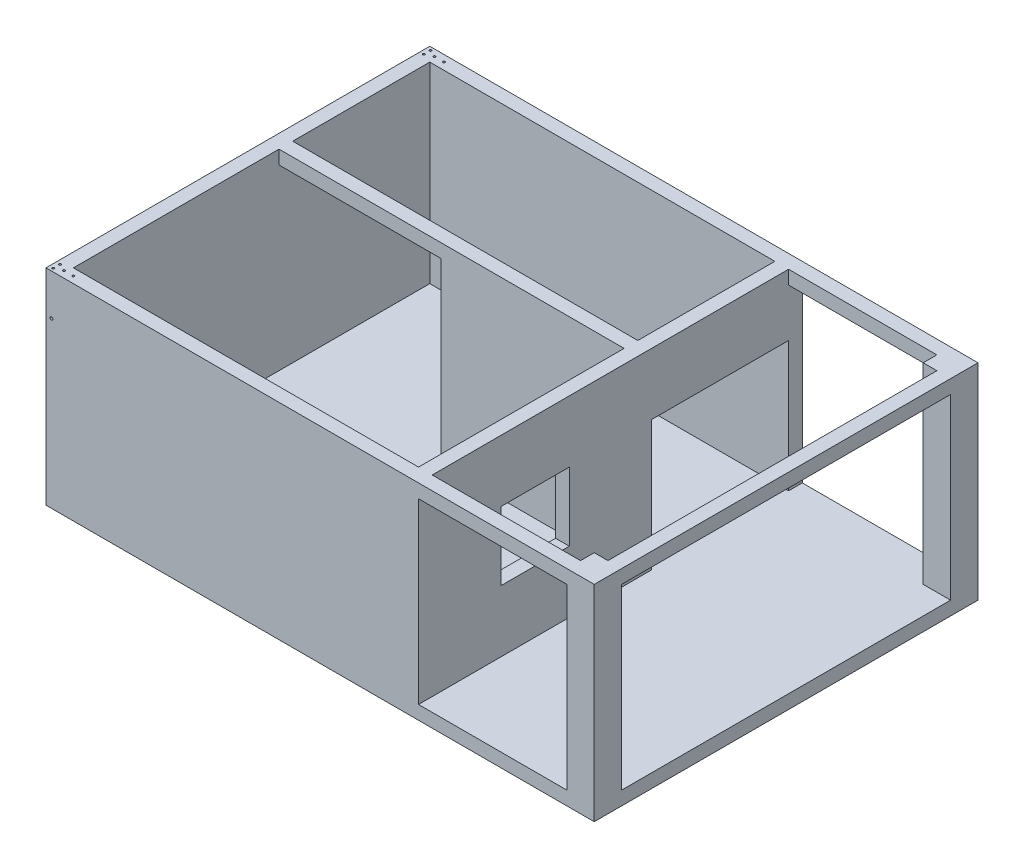
SolidWorks part; units mm, degrees
material "Pine"
ref_plane "Front Plane" through (0, 0, 0) normal (0, 0, 1) x (1, 0, 0)
ref_plane "Top Plane" through (0, 0, 0) normal (0, 1, 0) x (1, 0, 0)
ref_plane "Right Plane" through (0, 0, 0) normal (1, 0, 0) x (0, 0, -1)
sketch "Sketch1" plane through (0, 0, 0) normal (0, 1, 0) x (1, 0, 0)
  line L1 (0, 0) -> (2000, 0)
  line L2 (0, 0) -> (0, 1400)
  line L3 (0, 1400) -> (2000, 1400)
  line L4 (2000, 0) -> (2000, 1400)
  dimension "D1" = 2000
  dimension "D2" = 1400
extrude "Boss-Extrude1" add sketch "Sketch1" along normal blind 50
sketch "Sketch2" plane through (0, 50, 0) normal (0, 1, 0) x (1, 0, 0)
  line L0 (0, 700) -> (2000, 700) construction
  line L1 (2000, 1400) -> (1900, 1400)
  line L2 (2000, 1400) -> (2000, 1300)
  line L3 (2000, 1300) -> (1900, 1300)
  line L4 (1900, 1400) -> (1900, 1300)
  line L5 (0, 1400) -> (0, 0) construction
  line L6 (2000, 0) -> (2000, 1400) construction
  line L7 (2000, 100) -> (1900, 100)
  line L8 (1900, 0) -> (1900, 100)
  line L9 (2000, 0) -> (1900, 0)
  line L10 (2000, 0) -> (2000, 100)
  line L11 (0, 1350) -> (1359, 1350)
  line L12 (0, 0) -> (1359, 0)
  line L13 (0, 0) -> (0, 50)
  line L14 (0, 50) -> (1359, 50)
  line L15 (1359, 0) -> (1359, 50)
  line L16 (1359, 1400) -> (1359, 1350)
  line L17 (0, 1400) -> (1359, 1400)
  line L18 (0, 1400) -> (0, 1350)
  line L20 (0, 1350) -> (50, 1350)
  line L21 (0, 1350) -> (0, 50)
  line L22 (0, 50) -> (50, 50)
  line L23 (50, 1350) -> (50, 50)
  line L24 (641, 850) -> (1359, 850)
  line L25 (641, 850) -> (641, 800)
  line L26 (641, 800) -> (1359, 800)
  line L27 (1359, 850) -> (1359, 800)
  dimension "D1" = 100
  dimension "D2" = 100
  dimension "D3" = 1359
  dimension "D4" = 50
  dimension "D5" = 50
  dimension "D6" = 718
  dimension "D7" = 50
  dimension "D8" = 591
  dimension "D9" = 500
extrude "Boss-Extrude2" add sketch "Sketch2" along normal blind 700 contours L11 L16 L17 L18 | L21 L20 L23 L22 | L13 L12 L15 L14 | L25 L24 L27 L26 | L2 L1 L4 L3 | L7 L8 L9 L10
sketch "Sketch3" plane through (641, 0, 0) normal (-1, 0, 0) x (0, 0, 1)
  line L0 (-800, 750) -> (-800, 50) construction
  line L1 (-850, 750) -> (-800, 750)
  line L2 (-850, 750) -> (-850, 700)
  line L3 (-850, 700) -> (-800, 700)
  line L4 (-800, 750) -> (-800, 700)
  dimension "D1" = 50
extrude "Boss-Extrude3" add sketch "Sketch3" along normal up to surface (591 mm away) up to face at (50, 400, -700)
sketch "Sketch4" plane through (0, 50, 0) normal (0, 1, 0) x (1, 0, 0)
  line L0 (50, 50) -> (1359, 50) construction
  line L1 (1359, 800) -> (1309, 800)
  line L2 (1359, 800) -> (1359, 50)
  line L3 (1359, 50) -> (1309, 50)
  line L4 (1309, 800) -> (1309, 50)
  dimension "D1" = 50
extrude "Boss-Extrude4" add sketch "Sketch4" along normal up to vertex (700 mm away) up to point (1359, 750, -50)
sketch "Sketch5" plane through (1359, 0, 0) normal (1, 0, 0) x (0, 0, -1)
  line L1 (300, 525) -> (550, 525)
  line L2 (300, 525) -> (300, 275)
  line L3 (300, 275) -> (550, 275)
  line L4 (550, 525) -> (550, 275)
  line L5 (850, 750) -> (0, 750) construction
  line L6 (850, 750) -> (850, 50) construction
  dimension "D1" = 250
  dimension "D2" = 250
  dimension "D3" = 225
  dimension "D4" = 300
extrude "Cut-Extrude1" cut sketch "Sketch5" against normal blind 700
sketch "Sketch6" plane through (0, 0, -1350) normal (0, 0, 1) x (1, 0, 0)
  line L1 (1359, 750) -> (1309, 750)
  line L2 (1359, 750) -> (1359, 525)
  line L3 (1359, 525) -> (1309, 525)
  line L4 (1309, 750) -> (1309, 525)
  dimension "D1" = 225
  dimension "D2" = 50
extrude "Boss-Extrude5" add sketch "Sketch6" along normal up to surface (500 mm away) up to face at (683.3333, 500, -850)
sketch "Sketch8" plane through (1359, 0, 0) normal (1, 0, 0) x (0, 0, -1)
  line L0 (700, 750) -> (700, 0) construction
  line L1 (0, 750) -> (50, 750)
  line L2 (0, 750) -> (0, 700)
  line L3 (0, 700) -> (50, 700)
  line L4 (50, 750) -> (50, 700)
  line L5 (1400, 750) -> (0, 750) construction
  line L6 (0, 0) -> (1400, 0) construction
  line L7 (1400, 700) -> (1350, 700)
  line L8 (1350, 750) -> (1350, 700)
  line L9 (1400, 750) -> (1350, 750)
  line L10 (1400, 750) -> (1400, 700)
  dimension "D1" = 50
  dimension "D2" = 50
extrude "Boss-Extrude6" add sketch "Sketch8" along direction (-1, 0, 0) on the side of the normal up to surface (541 mm away) contours L2 L1 L4 L3 | L7 L8 L9 L10 up to face at (1900, 400, -50)
sketch "Sketch9" plane through (0, 0, -1300) normal (0, 0, 1) x (1, 0, 0)
  line L1 (2000, 750) -> (1950, 750)
  line L2 (2000, 750) -> (2000, 700)
  line L3 (2000, 700) -> (1950, 700)
  line L4 (1950, 750) -> (1950, 700)
  dimension "D1" = 50
  dimension "D2" = 50
extrude "Boss-Extrude7" add sketch "Sketch9" along normal up to surface (1200 mm away) up to face at (1950, 400, -100)
sketch "Sketch11" plane through (0, 0, 0) normal (0, 0, 1) x (1, 0, 0)
  line L0 (2000, 750) -> (0, 750) construction
  line L1 (0, 750) -> (0, 0) construction
  circle A0 centre (20, 600) radius 5
  dimension "D1" = 10
  dimension "D2" = 150
  dimension "D3" = 20
extrude "Cut-Extrude3" cut sketch "Sketch11" against normal through all both and the other way through all
sketch "Sketch10" plane through (0, 750, 0) normal (0, 1, 0) x (1, 0, 0)
  line L27 (0.007, 1400.0023) -> (135.624, 1389.3162)
  line L29 (-0.0259, 35.8312) -> (135.5911, 25.1452)
  line L30 (-0.0117, 26.8312) -> (-0.0259, 35.8312)
  line L31 (135.606, 15.7452) -> (135.6132, 11.1452)
  line L32 (135.6132, 11.1452) -> (0.0306, 0.0313)
  line L33 (0.0306, 0.0313) -> (0.0164, 9.0312)
  line L34 (0.0164, 9.0312) -> (-8.4836, 9.0178)
  line L35 (-8.4836, 9.0178) -> (-8.5117, 26.8178)
  line L45 (-8.5117, 26.8178) -> (-0.0117, 26.8312)
  line L46 (135.5911, 25.1452) -> (135.5984, 20.5452)
  line L47 (135.6132, 11.1452) -> (0.0306, 0.0313)
  line L48 (135.606, 15.7452) -> (135.6132, 11.1452)
  line L49 (135.5911, 25.1452) -> (135.5984, 20.5452)
  line L50 (-8.5117, 26.8178) -> (-0.0117, 26.8312)
  line L51 (-8.4836, 9.0178) -> (-8.5117, 26.8178)
  line L52 (0.0164, 9.0312) -> (-8.4836, 9.0178)
  line L53 (0.0306, 0.0313) -> (0.0164, 9.0312)
  line L54 (0.0212, 1391.0023) -> (0.007, 1400.0023)
  line L55 (135.6388, 1379.9162) -> (135.6461, 1375.3162)
  line L56 (135.6461, 1375.3162) -> (0.0635, 1364.2023)
  line L57 (0.0635, 1364.2023) -> (0.0493, 1373.2023)
  line L58 (0.0493, 1373.2023) -> (-8.4507, 1373.1889)
  line L59 (-8.4507, 1373.1889) -> (-8.4788, 1390.9889)
  line L60 (-8.4788, 1390.9889) -> (0.0212, 1391.0023)
  line L61 (135.624, 1389.3162) -> (135.6313, 1384.7162)
  line L62 (135.6461, 1375.3162) -> (0.0635, 1364.2023)
  line L63 (135.6388, 1379.9162) -> (135.6461, 1375.3162)
  line L64 (135.624, 1389.3162) -> (135.6313, 1384.7162)
  line L65 (-8.4788, 1390.9889) -> (0.0212, 1391.0023)
  line L66 (-8.4507, 1373.1889) -> (-8.4788, 1390.9889)
  line L67 (0.0493, 1373.2023) -> (-8.4507, 1373.1889)
  line L68 (0.0635, 1364.2023) -> (0.0493, 1373.2023)
  arc A11 (135.5984, 20.5452) -> (135.606, 15.7452) centre (135.6022, 18.1452) cw
  circle A13 centre (14.6164, 9.0543) radius 2.764
  circle A14 centre (120.6022, 18.1215) radius 2.4
  circle A15 centre (72.6023, 18.0458) radius 2.4
  circle A16 centre (24.5883, 26.87) radius 2.515
  arc A17 (135.5984, 20.5452) -> (135.606, 15.7452) centre (135.6022, 18.1452) cw
  arc A18 (135.6313, 1384.7162) -> (135.6388, 1379.9162) centre (135.635, 1382.3162) cw
  circle A19 centre (14.6492, 1373.2253) radius 2.764
  circle A20 centre (120.6351, 1382.2926) radius 2.4
  circle A21 centre (72.6351, 1382.2168) radius 2.4
  circle A22 centre (24.6211, 1391.0411) radius 2.515
  arc A23 (135.6313, 1384.7162) -> (135.6388, 1379.9162) centre (135.635, 1382.3162) cw
extrude "Cut-Extrude2" [suppressed] cut sketch "Sketch10" against normal blind 10 contours A13 | A16 | A15 | A14 | A19 | A22 | A21 | A20
sketch "Sketch12" plane through (0, 750, 0) normal (0, 1, 0) x (1, 0, 0)
  line L1 (-5, 1396) -> (-5, 1356)
  line L2 (0, 0) -> (0, 1400) construction
  line L3 (-5, 1376) -> (14.5, 1376) construction
  line L4 (14.5, 1388) -> (14.5, 1364) construction
  line L5 (14.5, 1376) -> (41.5, 1376) construction
  line L6 (41.5, 1376) -> (75.5, 1376) construction
  line L7 (-5, 44) -> (-5, 4)
  line L8 (-5, 24) -> (14.5, 24) construction
  line L9 (14.5, 36) -> (14.5, 12) construction
  line L10 (14.5, 24) -> (41.5, 24) construction
  line L11 (41.5, 24) -> (75.5, 24) construction
  circle A4 centre (14.5, 36) radius 4
  circle A5 centre (14.5, 12) radius 4
  circle A6 centre (41.5, 24) radius 4
  circle A7 centre (75.5, 24) radius 4
  circle A8 centre (14.5, 1388) radius 4
  circle A9 centre (14.5, 1364) radius 4
  circle A10 centre (41.5, 1376) radius 4
  circle A11 centre (75.5, 1376) radius 4
  point P9 (14.5, 1376)
  point P24 (14.5, 24)
  dimension "D5" = 27
  dimension "D10" = 8
  dimension "D4" = 8
  dimension "D2" = 19.5
  dimension "D3" = 24
  dimension "D6" = 34
  dimension "D7" = 40
  dimension "D8" = 19.5
  dimension "D9" = 24
  dimension "D11" = 27
  dimension "D12" = 34
  dimension "D13" = 5
  dimension "D14" = 4
  dimension "D15" = 40
  dimension "D16" = 5
  dimension "D17" = 4
extrude "Cut-Extrude4" cut sketch "Sketch12" against normal blind 10 and the other way through all contours A11 | A4 | A5 | A6 | A7 | A10 | A9 | A8 region at (14.5, 750, -36) region at (14.5, 750, -12) region at (41.5, 750, -24) region at (75.5, 750, -24) region at (14.5, 750, -1388) region at (14.5, 750, -1364) region at (41.5, 750, -1376) region at (75.5, 750, -1376)
